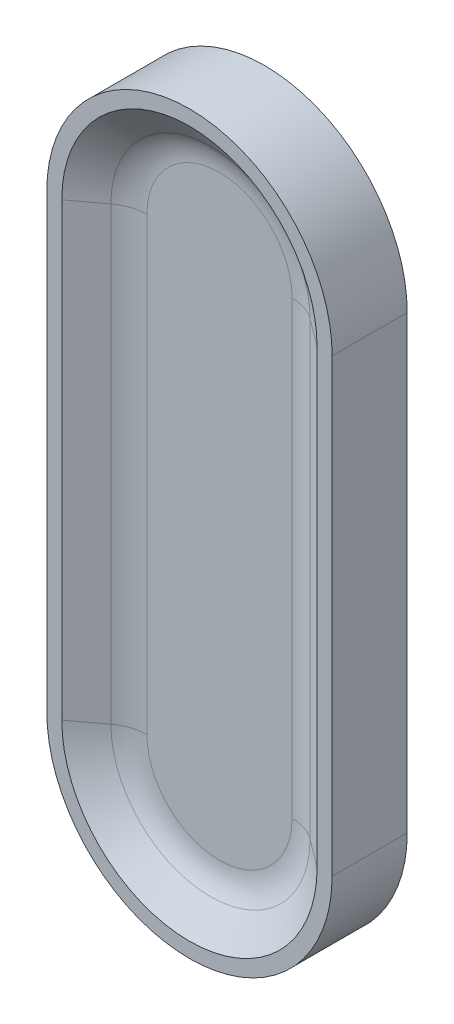
SolidWorks part; units mm, degrees
ref_plane "Ön Düzlem" through (0, 0, 0) normal (0, 0, 1) x (1, 0, 0)
ref_plane "Üst Düzlem" through (0, 0, 0) normal (0, 1, 0) x (1, 0, 0)
ref_plane "Sağ Düzlem" through (0, 0, 0) normal (1, 0, 0) x (0, 0, -1)
sketch "Çizim1" plane through (0, 0, 0) normal (0, 0, 1) x (1, 0, 0)
  line L0 (0, -15) -> (0, 15) construction
  line L1 (-9.5, -15) -> (-9.5, 15)
  line L2 (9.5, -15) -> (9.5, 15)
  arc A0 (-9.5, -15) -> (9.5, -15) centre (0, -15) ccw
  arc A1 (9.5, 15) -> (-9.5, 15) centre (0, 15) ccw
  point P2 (0, 0)
  dimension "D1" = 9.5
  dimension "D2" = 30
extrude "Yükseklik-Ekstrüzyon1" add sketch "Çizim1" along normal blind 5
sketch "Çizim2" plane through (0, 0, 5) normal (0, 0, 1) x (1, 0, 0)
  line L0 (-4.5, 15) -> (-4.5, -15)
  line L1 (4.5, -15) -> (4.5, 15)
  line L2 (9.5, -15) -> (9.5, 15)
  line L3 (-9.5, 15) -> (-9.5, -15)
  line L4 (9.5, -15) -> (9.5, 15)
  line L5 (-9.5, 15) -> (-9.5, -15)
  arc A0 (4.5, 15) -> (-4.5, 15) centre (0, 15) ccw
  arc A1 (-4.5, -15) -> (4.5, -15) centre (0, -15) ccw
  arc A2 (-9.5, -15) -> (9.5, -15) centre (0, -15) ccw
  arc A3 (9.5, 15) -> (-9.5, 15) centre (0, 15) ccw
  arc A4 (-9.5, -15) -> (9.5, -15) centre (0, -15) ccw
  arc A5 (9.5, 15) -> (-9.5, 15) centre (0, 15) ccw
  dimension "D1" = 0
  dimension "D2" = 5
extrude "Kes-Ekstrüzyon1" cut sketch "Çizim2" against normal blind 2 contours L0 A1 L1 A0 region at (0, 0, 5)
chamfer "Pah1" distance 4 distance2 3 4 edges at (0, -19.5, 5) (4.5, 0, 5) (-4.5, 0, 5) (0, 19.5, 5) first distance on face at (0, 0, 5)
fillet "Radyus1" radius 3 4 edges at (5.8333, 0, 3) (0, -20.8333, 3) (-5.8333, 0, 3) (0, 20.8333, 3)
